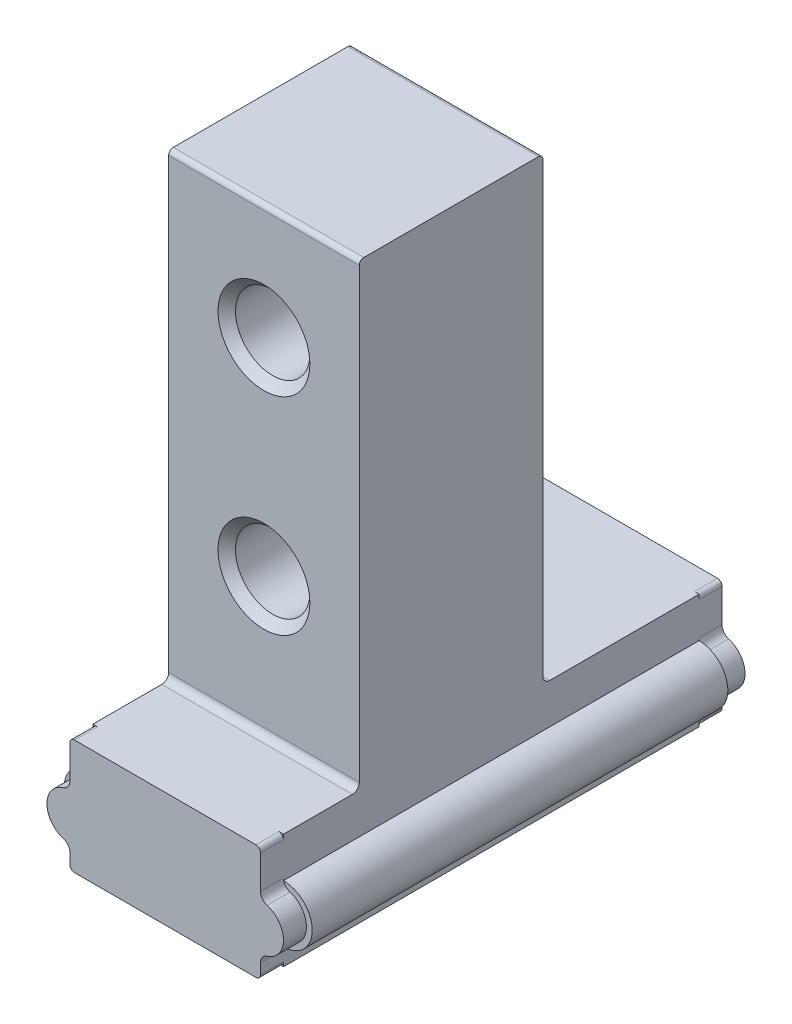
SolidWorks part; units mm, degrees
ref_plane "Front Plane" through (0, 0, 0) normal (0, 0, 1) x (1, 0, 0)
ref_plane "Top Plane" through (0, 0, 0) normal (0, 1, 0) x (1, 0, 0)
ref_plane "Right Plane" through (0, 0, 0) normal (1, 0, 0) x (0, 0, -1)
sketch "Sketch1" plane through (0, 0, 0) normal (1, 0, 0) x (0, 0, -1)
  line L0 (-18.1, 5) -> (-18.1, 0)
  line L1 (-18.1, 0) -> (0, 0)
  line L2 (0, 0) -> (0, 5)
  line L3 (0, 5) -> (-6.5, 5)
  line L4 (-6.8, 5.3) -> (-6.8, 24.8)
  line L5 (-7, 25) -> (-14.6, 25)
  line L6 (-14.8, 24.8) -> (-14.8, 5.3)
  line L7 (-15.1, 5) -> (-18.1, 5)
  arc A0 (-6.5, 5) -> (-6.8, 5.3) centre (-6.5, 5.3) cw
  arc A1 (-6.8, 24.8) -> (-7, 25) centre (-7, 24.8) ccw
  arc A2 (-14.6, 25) -> (-14.8, 24.8) centre (-14.6, 24.8) ccw
  arc A3 (-14.8, 5.3) -> (-15.1, 5) centre (-15.1, 5.3) cw
extrude "Boss-Extrude1" add sketch "Sketch1" against normal blind 4.15 and the other way blind 4.15
sketch "Sketch2" plane through (0, 0, 0) normal (1, 0, 0) x (0, 0, -1)
  line L0 (-14.8, 20) -> (-14.8, 22)
  line L1 (-14.8, 22) -> (-14.421, 21.621)
  line L2 (-14.421, 21.621) -> (-7.179, 21.621)
  line L3 (-7.179, 21.621) -> (-6.8, 22)
  line L4 (-6.8, 22) -> (-6.8, 20)
  line L5 (-6.8, 20) -> (-14.8, 20)
  line L6 (-6.8, 20) -> (-14.8, 20) construction
revolve "Cut-Revolve1" cut sketch "Sketch2" angle 360 about L6 reverse direction yes
cosmetic thread "Cosmetic Thread1" parameters "D1"=8, "D2"=4
sketch "Sketch3" plane through (0, 0, 0) normal (1, 0, 0) x (0, 0, -1)
  line L0 (-14.8, 11) -> (-14.8, 13)
  line L1 (-14.8, 13) -> (-14.421, 12.621)
  line L2 (-14.421, 12.621) -> (-7.179, 12.621)
  line L3 (-7.179, 12.621) -> (-6.8, 13)
  line L4 (-6.8, 13) -> (-6.8, 11)
  line L5 (-6.8, 11) -> (-14.8, 11)
  line L6 (-6.8, 11) -> (-14.8, 11) construction
revolve "Cut-Revolve2" cut sketch "Sketch3" angle 360 about L6 reverse direction yes
cosmetic thread "Cosmetic Thread2" parameters "D1"=8, "D2"=4
ref_plane "Plane1" through (0, 0, 10.8) normal (0, 0, 1) x (1, 0, 0)
sketch "Sketch4" plane through (0, 0, 0) normal (0, 0, 1) x (1, 0, 0)
  line L0 (-4.15, 0.75) -> (4.15, 0.75)
  line L1 (4.15, 3.25) -> (-4.15, 3.25)
  arc A0 (-4.15, 3.25) -> (-4.15, 0.75) centre (-4.15, 2) ccw
  arc A1 (4.15, 0.75) -> (4.15, 3.25) centre (4.15, 2) ccw
extrude "Boss-Extrude2" add sketch "Sketch4" along normal blind 18.1
sketch "Sketch5" plane through (0, 0, 0) normal (0, 0, 1) x (1, 0, 0)
  line L0 (-4.15, 0.6584) -> (-4.15, 0.2)
  line L1 (-3.95, 0) -> (3.95, 0)
  line L2 (4.15, 0.2) -> (4.15, 0.6584)
  line L3 (4.15, 3.3416) -> (4.15, 4.8)
  line L4 (3.95, 5) -> (-3.95, 5)
  line L5 (-4.15, 4.8) -> (-4.15, 3.3416)
  arc A0 (-4.4357, 2.9583) -> (-4.4357, 1.0417) centre (-4.15, 2) ccw
  arc A1 (-4.4357, 1.0417) -> (-4.15, 0.6584) centre (-4.55, 0.6584) cw
  arc A2 (-4.15, 0.2) -> (-3.95, 0) centre (-3.95, 0.2) ccw
  arc A3 (3.95, 0) -> (4.15, 0.2) centre (3.95, 0.2) ccw
  arc A4 (4.15, 0.6584) -> (4.4357, 1.0417) centre (4.55, 0.6584) cw
  arc A5 (4.4357, 1.0417) -> (4.4357, 2.9583) centre (4.15, 2) ccw
  arc A6 (4.4357, 2.9583) -> (4.15, 3.3416) centre (4.55, 3.3416) cw
  arc A7 (4.15, 4.8) -> (3.95, 5) centre (3.95, 4.8) ccw
  arc A8 (-3.95, 5) -> (-4.15, 4.8) centre (-3.95, 4.8) ccw
  arc A9 (-4.15, 3.3416) -> (-4.4357, 2.9583) centre (-4.55, 3.3416) cw
extrude "Boss-Extrude3" add sketch "Sketch5" against normal blind 1
ref_plane "Plane2" through (0, 0, 18.1) normal (0, 0, 1) x (1, 0, 0)
sketch "Sketch6" plane through (0, 0, 18.1) normal (0, 0, 1) x (1, 0, 0)
  line L0 (-4.15, 0.6584) -> (-4.15, 0.2)
  line L1 (-3.95, 0) -> (3.95, 0)
  line L2 (4.15, 0.2) -> (4.15, 0.6584)
  line L3 (4.15, 3.3416) -> (4.15, 4.8)
  line L4 (3.95, 5) -> (-3.95, 5)
  line L5 (-4.15, 4.8) -> (-4.15, 3.3416)
  arc A0 (-4.4357, 2.9583) -> (-4.4357, 1.0417) centre (-4.15, 2) ccw
  arc A1 (-4.4357, 1.0417) -> (-4.15, 0.6584) centre (-4.55, 0.6584) cw
  arc A2 (-4.15, 0.2) -> (-3.95, 0) centre (-3.95, 0.2) ccw
  arc A3 (3.95, 0) -> (4.15, 0.2) centre (3.95, 0.2) ccw
  arc A4 (4.15, 0.6584) -> (4.4357, 1.0417) centre (4.55, 0.6584) cw
  arc A5 (4.4357, 1.0417) -> (4.4357, 2.9583) centre (4.15, 2) ccw
  arc A6 (4.4357, 2.9583) -> (4.15, 3.3416) centre (4.55, 3.3416) cw
  arc A7 (4.15, 4.8) -> (3.95, 5) centre (3.95, 4.8) ccw
  arc A8 (-3.95, 5) -> (-4.15, 4.8) centre (-3.95, 4.8) ccw
  arc A9 (-4.15, 3.3416) -> (-4.4357, 2.9583) centre (-4.55, 3.3416) cw
extrude "Boss-Extrude4" add sketch "Sketch6" along normal blind 1
sketch "Sketch7" plane through (0, 0, 0) normal (1, 0, 0) x (0, 0, -1)
  line L0 (-4, -2) -> (-2, -2)
  line L1 (-2, -2) -> (-2, 0)
  line L2 (-2, 0) -> (-4, 0)
  line L3 (-4, 0) -> (-4, -2)
extrude "Boss-Extrude5" add sketch "Sketch7" against normal blind 1 and the other way blind 1
ref_plane "Plane3" through (0, 0, 2) normal (0, 0, 1) x (1, 0, 0)
ref_plane "Plane4" through (0, 0, 14.8) normal (0, 0, 1) x (1, 0, 0)
ref_plane "ANBAU XY" through (0, 0, 2) normal (0, 0, -1) x (-1, 0, 0)
ref_plane "ANBAU XZ" through (0, 0, 0) normal (0, 1, 0) x (1, 0, 0)
ref_plane "ANBAU YZ" through (0, 0, 0) normal (1, 0, 0) x (0, 0, -1)
ref_axis "ANBAU X" through (-80.9, 0, 2) along (1, 0, 0)
ref_axis "ANBAU Y" through (0, 50, 2) along (0, -1, 0)
ref_axis "ANBAU Z" through (0, 0, -80.9) along (0, 0, 1)
sketch3d "ANBAU"
  point P0 (0, 0, 2)
other "Freeze***"
